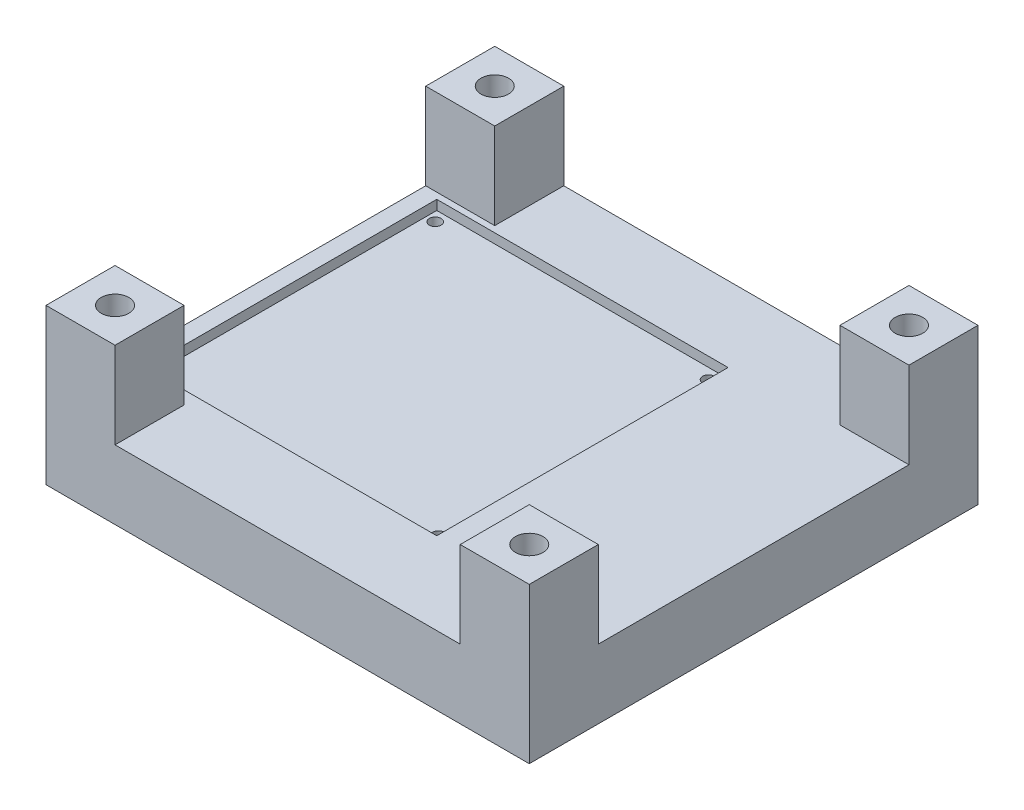
SolidWorks part; units mm, degrees
ref_plane "Front Plane" through (0, 0, 0) normal (0, 0, 1) x (1, 0, 0)
ref_plane "Top Plane" through (0, 0, 0) normal (0, 1, 0) x (1, 0, 0)
ref_plane "Right Plane" through (0, 0, 0) normal (1, 0, 0) x (0, 0, -1)
sketch "Sketch2" plane through (0, 0, 0) normal (0, 1, 0) x (1, 0, 0)
  line L1 (0, 0) -> (177.8, 0)
  line L2 (0, 0) -> (0, -165.1)
  line L3 (0, -165.1) -> (177.8, -165.1)
  line L4 (177.8, 0) -> (177.8, -165.1)
extrude "Boss-Extrude1" add sketch "Sketch2" along normal blind 25.4
ref_axis "Axis1" through (0, 25.4, 82.55) along (1, 0, 0)
ref_axis "Axis2" through (88.9, 25.4, 0) along (0, 0, 1)
ref_plane "Plane1" through (88.9, 0, 0) normal (-1, 0, 0) x (0, 0, 1)
ref_plane "Plane2" through (0, 0, 82.55) normal (0, 0, -1) x (-1, 0, 0)
sketch "Sketch6" plane through (0, 25.4, 0) normal (0, 1, 0) x (1, 0, 0)
  line L1 (0, 0) -> (25.4, 0)
  line L2 (0, 0) -> (0, -25.4)
  line L3 (0, -25.4) -> (25.4, -25.4)
  line L4 (25.4, 0) -> (25.4, -25.4)
extrude "Boss-Extrude2" add sketch "Sketch6" along normal blind 31.75
mirror "Mirror1" about plane through (0, 0, 82.55) normal (0, 0, -1) of "Boss-Extrude2"
mirror "Mirror2" about plane through (88.9, 0, 0) normal (-1, 0, 0) of "Mirror1"
sketch "Sketch9" plane through (0, 25.4, 0) normal (0, 1, 0) x (1, 0, 0)
  line L0 (0, -25.4) -> (25.4, -25.4) construction
  line L4 (6.35, -27.683) -> (113.538, -27.683)
  line L5 (6.35, -27.683) -> (6.35, -134.871)
  line L6 (6.35, -134.871) -> (113.538, -134.871)
  line L7 (113.538, -27.683) -> (113.538, -134.871)
  point P0 (12.7, -25.4)
extrude "Cut-Extrude3" cut sketch "Sketch9" against normal blind 3.556
sketch "Sketch10" plane through (0, 21.844, 0) normal (0, 1, 0) x (1, 0, 0)
  line L0 (6.35, -27.683) -> (9.663, -27.683)
  line L1 (113.538, -27.683) -> (6.35, -27.683) construction
  line L2 (9.663, -27.683) -> (9.663, -31.5739)
  ellipse E0 centre (9.663, -31.5739) end of major axis (10.8613, -29.778) minor radius 2.159
ref_axis "Axis3" through (59.944, 25.4, 27.683) along (0, 0, 1)
ref_axis "Axis4" through (6.35, 25.4, 81.277) along (1, 0, 0)
ref_plane "Plane15" through (0, 0, 81.277) normal (0, 0, 1) x (1, 0, 0)
ref_plane "Plane16" through (59.944, 0, 0) normal (-1, 0, 0) x (0, 0, 1)
extrude "Cut-Extrude4" cut sketch "Sketch10" against normal blind 20.32 contours E0
mirror "Mirror3" about plane through (0, 0, 81.277) normal (0, 0, 1) of "Cut-Extrude4"
mirror "Mirror4" about plane through (59.944, 0, 0) normal (-1, 0, 0) of "Mirror3"
sketch "Sketch14" plane through (0, 57.15, 0) normal (0, 1, 0) x (1, 0, 0)
  circle A0 centre (12.7, -12.7) radius 5.08
extrude "Cut-Extrude5" cut sketch "Sketch14" against normal blind 20.32
mirror "Mirror5" about plane through (88.9, 0, 0) normal (-1, 0, 0) of "Cut-Extrude5"
mirror "Mirror6" about plane through (0, 0, 82.55) normal (0, 0, -1) of "Mirror5"
